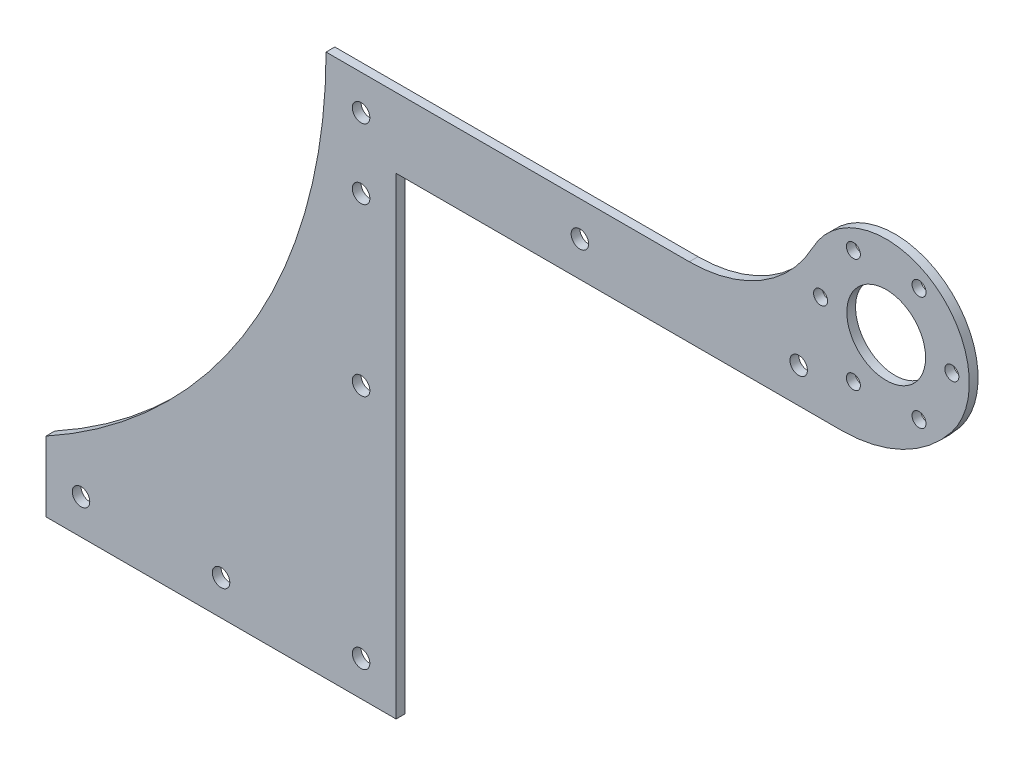
SolidWorks part; units mm, degrees
material "6061-T6 (SS)"
ref_plane "Front Plane" through (0, 0, 0) normal (0, 0, 1) x (1, 0, 0)
ref_plane "Top Plane" through (0, 0, 0) normal (0, 1, 0) x (1, 0, 0)
ref_plane "Right Plane" through (0, 0, 0) normal (1, 0, 0) x (0, 0, -1)
sketch "Sketch1" plane through (0, 0, 0) normal (0, 0, 1) x (1, 0, 0)
  line L0 (0, 0) -> (-127, 0)
  line L1 (-127, 0) -> (-127, 25.4)
  line L3 (-25.4, 196.85) -> (0, 196.85)
  line L4 (0, 196.85) -> (0, 0) construction
  line L5 (-127, 12.7) -> (0, 12.7) construction
  line L6 (-12.7, 196.85) -> (-12.7, 0) construction
  line L7 (0, 196.85) -> (106.3625, 196.85)
  line L8 (161.533, 171.45) -> (0, 171.45)
  line L9 (0, 171.45) -> (0, 0)
  line L10 (-12.7, 184.15) -> (146.05, 184.15) construction
  circle A0 centre (-12.7, 12.7) radius 3.175
  circle A1 centre (-12.7, 184.15) radius 3.175
  circle A2 centre (-114.3, 12.7) radius 3.175
  circle A3 centre (-63.5, 12.7) radius 3.175
  circle A4 centre (-12.7, 98.425) radius 3.175
  arc A5 (-25.4, 196.85) -> (-127, 25.4) centre (-220.8609, 196.85) cw
  circle A7 centre (177.8, 209.55) radius 14.2875
  arc A8 (201.5749, 190.9885) -> (151.186, 223.7441) centre (177.8, 209.55) ccw
  circle A11 centre (177.8, 209.55) radius 23.8125 construction
  circle A12 centre (201.6125, 209.55) radius 2.54
  circle A13 centre (189.7062, 188.9278) radius 2.54
  circle A14 centre (165.8937, 188.9278) radius 2.54
  circle A15 centre (153.9875, 209.55) radius 2.54
  circle A16 centre (165.8937, 230.1722) radius 2.54
  circle A17 centre (189.7062, 230.1722) radius 2.54
  circle A18 centre (66.675, 184.15) radius 3.175
  circle A19 centre (-12.7, 158.75) radius 3.175
  arc A20 (106.3625, 196.85) -> (151.186, 223.7441) centre (106.3625, 247.65) ccw
  arc A21 (201.5749, 190.9885) -> (161.533, 171.45) centre (161.533, 222.25) cw
  circle A22 centre (146.05, 184.15) radius 3.175
  point P46 (177.8, 209.55)
  point P50 (0, 0)
  dimension "D4" = 6.35
  dimension "D8" = 28.575
  dimension "D10" = 60.325
  dimension "D11" = 25.4
  dimension "D12" = 47.625
  dimension "D13" = 5.08
  dimension "D17" = 50.8
  dimension "D18" = 50.8
  dimension "D1" = 25.4
  dimension "D2" = 196.85
  dimension "D3" = 127
  dimension "D5" = 12.7
  dimension "D6" = 12.7
  dimension "D7" = 190.5
  dimension "D9" = 25.4
  dimension "D15" = 158.75
  dimension "D16" = 25.4
  dimension "D14" = 6
base flange "Base-Flange1" sketch "Sketch1" thickness 3.175 reverse thickness direction no parameters "D1"=0.7366
sketch "Bend-Lines1" [suppressed] plane through (0, 0, 0) normal (0, 1, 0) x (1, 0, 0)
sketch "Bounding-Box1" [suppressed] plane through (0, 0, 0) normal (0, 1, 0) x (1, 0, 0)
sheet metal parameters "Sheet-Metal1" thickness 3.175 parameters "D1"=0.7366
flat pattern "Flat-Pattern1" [suppressed]
sketch "Bend-Lines2" plane through (0, 0, 0) normal (0, 1, 0) x (1, 0, 0)
sketch3d "Bounding-Box2" [suppressed]
  line L0 (153.6726, -260.2428, 0) -> (441.4615, 11.2885, 0) construction
  line L1 (43.4514, -143.4223, 0) -> (331.2404, 128.1091, 0) construction
  line L2 (153.6726, -260.2428, 0) -> (43.4514, -143.4223, 0) construction
  line L3 (441.4615, 11.2885, 0) -> (331.2404, 128.1091, 0) construction
